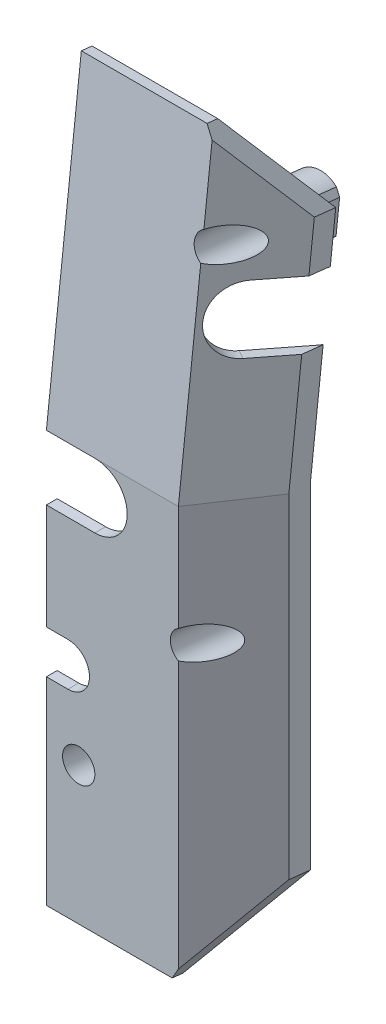
SolidWorks part; units mm, degrees
material "ABS"
ref_plane "Front Plane" through (0, 0, 0) normal (0, 0, 1) x (1, 0, 0)
ref_plane "Top Plane" through (0, 0, 0) normal (0, 1, 0) x (1, 0, 0)
ref_plane "Right Plane" through (0, 0, 0) normal (1, 0, 0) x (0, 0, -1)
sketch "Sketch1" plane through (0, 0, 0) normal (0, 0, 1) x (1, 0, 0)
  line L1 (0, -23.7112) -> (23.3397, -23.7112)
  line L2 (0, -23.7112) -> (0, -101.559)
  line L3 (0, -101.559) -> (23.3397, -101.559)
  line L4 (23.3397, -23.7112) -> (23.3397, -101.559)
extrude "Extrude1" add sketch "Sketch1" along normal blind 2
sketch "Sketch2" plane through (0, -0.3122, -2.7808) normal (0, 0.1116, 0.9938) x (1, 0, 0)
  line L1 (0, 33.0751) -> (23.3397, 33.0751)
  line L2 (0, 33.0751) -> (0, -25.3979)
  line L3 (0, -25.3979) -> (23.3397, -25.3979)
  line L4 (23.3397, 33.0751) -> (23.3397, -25.3979)
extrude "Extrude2" add sketch "Sketch2" along normal blind 2
sketch "Sketch3" plane through (17.5048, 0, 10.1064) normal (0.866, 0, 0.5) x (0.5, 0, -0.866)
  line L0 (7.8834, -104.4906) -> (28.9904, -88.1487)
  line L1 (28.9904, -88.1487) -> (28.9904, -25.9209)
  line L2 (28.9904, -25.9209) -> (7.8834, -23.3526)
  line L3 (7.8834, -23.3526) -> (7.8834, -104.4906)
  line L4 (28.9904, -88.1487) -> (28.4545, -88.5636) construction
  point P2 (0, 0)
extrude "Extrude3" add sketch "Sketch3" along normal blind 2
sketch "Sketch4" plane through (16.2931, 1.0495, 9.3481) normal (0.866, 0.0558, 0.4969) x (0.4959, 0.0319, -0.8678)
  line L0 (16.1567, 37.3027) -> (33.4767, 13.8866)
  line L1 (33.4767, 13.8866) -> (28.0567, -27.9242)
  line L2 (28.0567, -27.9242) -> (7.5025, -29.4562)
  line L3 (7.5025, -29.4562) -> (16.1567, 37.3027)
  point P2 (0, 0)
extrude "Extrude4" add sketch "Sketch4" along normal blind 2
sketch "Sketch5" plane through (32, 0, 0) normal (1, 0, 0) x (0, 0, -1)
  line L1 (-3.6781, -94.4767) -> (25.4941, -94.4767)
  line L2 (-3.6781, -94.4767) -> (-3.6781, 19.7758)
  line L3 (-3.6781, 19.7758) -> (25.4941, 19.7758)
  line L4 (25.4941, -94.4767) -> (25.4941, 19.7758)
extrude "Cut-Extrude1" cut sketch "Sketch5" along normal blind 2
sketch "Sketch6" plane through (0, -100.2949, 11.2597) normal (0, -0.9938, 0.1116) x (1, 0, 0)
  line L1 (-2.7117, -20.9529) -> (32.4638, -20.9529)
  line L2 (-2.7117, -20.9529) -> (-2.7117, 15.4027)
  line L3 (-2.7117, 15.4027) -> (32.4638, 15.4027)
  line L4 (32.4638, -20.9529) -> (32.4638, 15.4027)
extrude "Cut-Extrude3" cut sketch "Sketch6" along normal blind 9
sketch "Sketch7" plane through (0, 0, 2) normal (0, 0, 1) x (1, 0, 0)
  line L1 (-2.0227, -104.3379) -> (27.6176, -104.3379)
  line L2 (-2.0227, -104.3379) -> (-2.0227, -17.8423)
  line L3 (-2.0227, -17.8423) -> (27.6176, -17.8423)
  line L4 (27.6176, -104.3379) -> (27.6176, -17.8423)
extrude "Cut-Extrude4" cut sketch "Sketch7" along normal blind 9
sketch "Sketch8" plane through (0, -0.0891, -0.7932) normal (0, 0.1116, 0.9938) x (1, 0, 0)
  line L1 (-1.9319, -27.4261) -> (27.6043, -27.4261)
  line L2 (-1.9319, -27.4261) -> (-1.9319, 39.9017)
  line L3 (-1.9319, 39.9017) -> (27.6043, 39.9017)
  line L4 (27.6043, -27.4261) -> (27.6043, 39.9017)
extrude "Cut-Extrude5" cut sketch "Sketch8" along normal blind 9
sketch "Sketch9" plane through (19.2369, 0, 11.1064) normal (0.866, 0, 0.5) x (0.5, 0, -0.866)
  line L1 (3.8876, -34.5009) -> (27.1911, -34.5009)
  line L2 (3.8876, -34.5009) -> (3.8876, -16.7559)
  line L3 (3.8876, -16.7559) -> (27.1911, -16.7559)
  line L4 (27.1911, -34.5009) -> (27.1911, -16.7559)
extrude "Cut-Extrude6" cut sketch "Sketch9" along normal blind 9
sketch "Sketch10" plane through (18.0252, 1.161, 10.3419) normal (0.866, 0.0558, 0.4969) x (0.4959, 0.0319, -0.8678)
  line L1 (1.0658, -34.5401) -> (30.6717, -34.5401)
  line L2 (1.0658, -34.5401) -> (1.0658, -10.3301)
  line L3 (1.0658, -10.3301) -> (30.6717, -10.3301)
  line L4 (30.6717, -34.5401) -> (30.6717, -10.3301)
extrude "Cut-Extrude7" cut sketch "Sketch10" along normal blind 9
sketch "Sketch11" plane through (0, 32.8686, -3.69) normal (0, 0.9938, -0.1116) x (1, 0, 0)
  line L1 (34.1385, -25.981) -> (16.8582, -25.981)
  line L2 (34.1385, -25.981) -> (34.1385, 31.0629)
  line L3 (34.1385, 31.0629) -> (16.8582, 31.0629)
  line L4 (16.8582, -25.981) -> (16.8582, 31.0629)
extrude "Cut-Extrude8" cut sketch "Sketch11" along normal blind 9
sketch "Sketch12" plane through (31.8267, 18.2605, -2.05) normal (0.866, 0.4969, -0.0558) x (-0.0484, -0.0278, -0.9984)
  line L1 (-11.2492, 21.027) -> (35.3958, 21.027)
  line L2 (-11.2492, 21.027) -> (-11.2492, -5.5004)
  line L3 (-11.2492, -5.5004) -> (35.3958, -5.5004)
  line L4 (35.3958, 21.027) -> (35.3958, -5.5004)
extrude "Cut-Extrude9" cut sketch "Sketch12" along normal blind 9
sketch "Sketch13" plane through (61.2066, -35.117, 3.9424) normal (0.866, -0.4969, 0.0558) x (0.0484, -0.0278, -0.9984)
  line L1 (-2.0688, -86.5611) -> (25.8338, -86.5611)
  line L2 (-2.0688, -86.5611) -> (-2.0688, -49.7302)
  line L3 (-2.0688, -49.7302) -> (25.8338, -49.7302)
  line L4 (25.8338, -86.5611) -> (25.8338, -49.7302)
extrude "Cut-Extrude10" cut sketch "Sketch13" along normal blind 9
sketch "Sketch14" plane through (0, 0, 2) normal (0, 0, 1) x (1, 0, 0)
  line L0 (-5.731, -30.9696) -> (9, -30.9696) construction
  line L1 (-5.731, -24.9696) -> (9, -24.9696)
  line L2 (-5.731, -36.9696) -> (9, -36.9696)
  line L3 (0, -24.9696) -> (0, -101.3344) construction
  line L4 (0, -24.9696) -> (24.4944, -24.9696) construction
  arc A0 (-5.731, -24.9696) -> (-5.731, -36.9696) centre (-5.731, -30.9696) ccw
  arc A1 (9, -36.9696) -> (9, -24.9696) centre (9, -30.9696) ccw
  point P2 (1.6345, -30.9696)
  dimension "D1" = 6
  dimension "D2" = 9
  dimension "D3" = 6
extrude "Cut-Extrude11" cut sketch "Sketch14" against normal blind 9
sketch "Sketch15" plane through (18.0252, 1.161, 10.3419) normal (0.866, 0.0558, 0.4969) x (0.4959, 0.0319, -0.8678)
  line L0 (20.1779, 0.4736) -> (30.7584, -0.898) construction
  line L1 (20.9493, 6.4238) -> (31.5297, 5.0522)
  line L2 (19.4066, -5.4766) -> (29.987, -6.8482)
  line L3 (30.0414, 14.3319) -> (24.5925, -27.7008) construction
  arc A0 (20.9493, 6.4238) -> (19.4066, -5.4766) centre (20.1779, 0.4736) ccw
  arc A1 (29.987, -6.8482) -> (31.5297, 5.0522) centre (30.7584, -0.898) ccw
  point P2 (25.4682, -0.2122)
  dimension "D1" = 6
  dimension "D2" = 8
extrude "Cut-Extrude12" cut sketch "Sketch15" against normal blind 9
ref_plane "Plane1" through (0, -2.3204, -20.6684) normal (0, 0.1116, 0.9938) x (1, 0, 0)
sketch "Sketch16" plane through (0, -2.3204, -20.6684) normal (0, 0.1116, 0.9938) x (1, 0, 0)
  line L0 (29.8, 17.4856) -> (29.8, 11.5516)
  line L2 (2.2, -72.2995) -> (2.2, -78.7987)
  line L3 (29.8, 17.4856) -> (29.0724, 18.7459)
  line L4 (29.8, -43.8671) -> (29.8, -50.3663)
  line L5 (30, -23.3603) -> (30, 17.5392) construction
  line L9 (30, 17.5392) -> (23.3397, 29.0751) construction
  line L10 (2, -98.9249) -> (2, -24.9249) construction
  arc A2 (29.8, -43.8671) -> (29.8, -50.3663) centre (26, -47.1167) ccw
  arc A3 (29.0724, 18.7459) -> (29.8, 11.5516) centre (26, 14.8012) ccw
  arc A4 (2.2, -78.7987) -> (2.2, -72.2995) centre (6, -75.5491) ccw
  circle A5 centre (26, 14.8012) radius 1.6
  circle A6 centre (26, -47.1167) radius 1.6
  circle A7 centre (6, -75.5491) radius 1.6
  dimension "D1" = 10
  dimension "D4" = 3.2
  dimension "D2" = 0.2
  dimension "D3" = 0.2
  dimension "D5" = 0.2
extrude "Extrude5" add sketch "Sketch16" along normal up to next contours L3 A3 L0 A5 | L4 A2 A6 | L2 A4 A7 region at (29.6668, 12.1076, -22.2881) region at (10.8668, -77.3978, -12.2397) region at (29.6668, -49.1429, -15.4118)
sketch "Sketch18" plane through (0, -0.0891, -0.7932) normal (0, 0.1116, 0.9938) x (1, 0, 0)
  circle A0 centre (26, 14.8012) radius 3
  circle A1 centre (26, -47.1167) radius 3
  circle A2 centre (6, -75.5491) radius 3
  dimension "D1" = 6
extrude "Cut-Extrude13" cut sketch "Sketch18" against normal blind 16
sketch "Sketch19" plane through (0, 0, 2) normal (0, 0, 1) x (1, 0, 0)
  line L0 (-9.5464, -60.5875) -> (4, -60.5875) construction
  line L1 (-9.5464, -56.5875) -> (4, -56.5875)
  line L2 (-9.5464, -64.5875) -> (4, -64.5875)
  line L3 (0, -36.9696) -> (0, -101.3344) construction
  arc A0 (-9.5464, -56.5875) -> (-9.5464, -64.5875) centre (-9.5464, -60.5875) ccw
  arc A1 (4, -64.5875) -> (4, -56.5875) centre (4, -60.5875) ccw
  point P2 (-2.7732, -60.5875)
  dimension "D1" = 4
  dimension "D2" = 4
extrude "Cut-Extrude14" cut sketch "Sketch19" against normal blind 46
